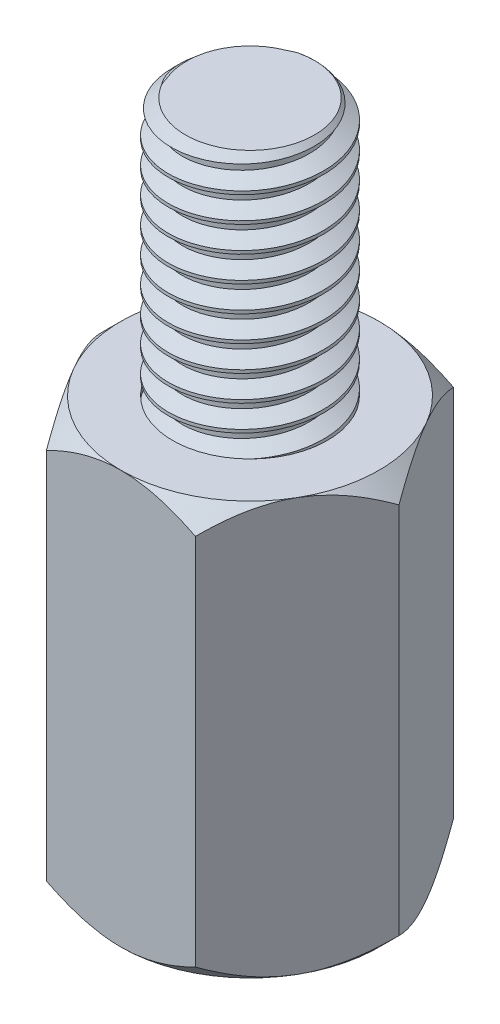
SolidWorks part; units mm, degrees
material "201 Acier inoxydable recuit (SS)"
ref_plane "Plan de face" through (0, 0, 0) normal (0, 0, 1) x (1, 0, 0)
ref_plane "Plan de dessus" through (0, 0, 0) normal (0, 1, 0) x (1, 0, 0)
ref_plane "Plan de droite" through (0, 0, 0) normal (1, 0, 0) x (0, 0, -1)
sketch "Esquisse1" plane through (0, 0, 0) normal (0, 1, 0) x (1, 0, 0)
  line L0 (-4.8113, 0) -> (4.4676, 0) construction
  line L1 (-2.8868, 0) -> (-1.4434, -2.5)
  line L2 (-1.4434, -2.5) -> (1.4434, -2.5)
  line L3 (1.4434, -2.5) -> (2.8868, 0)
  line L4 (2.8868, 0) -> (1.4434, 2.5)
  line L5 (1.4434, 2.5) -> (-1.4434, 2.5)
  line L6 (-1.4434, 2.5) -> (-2.8868, 0)
  line L7 (0, 4.1067) -> (0, -3.6256) construction
  circle A0 centre (0, 0) radius 2.5 construction
  dimension "D1" = 5
extrude "Adjustable height" add sketch "Esquisse1" along normal blind 4 and the other way blind 4
hole_wizard "Trou taraudé M31" positions "Esquisse2" profile "Esquisse3" tap size "M3" standard "ISO"
sketch "Esquisse2" plane through (0, -4, 0) normal (0, -1, 0) x (-1, 0, 0)
  point P0 (0, 0)
cosmetic thread "Filetage de perçage1" parameters "D1"=19.5, "D2"=3
sketch "Esquisse3" plane through (0, -4, 0) normal (1, 0, 0) x (0, 0, -1)
  line L0 (0, 0) -> (0, 20.7511)
  line L1 (0, 20.7511) -> (1.25, 20)
  line L2 (1.25, 20) -> (1.25, 0.5)
  line L3 (1.25, 0.5) -> (1.75, 0)
  line L5 (1.75, 0) -> (0, 0)
  line L6 (-1.25, 0.5) -> (-1.75, 0) construction
  line L10 (0, 20.7511) -> (-1.25, 20) construction
  line L11 (0, -6.35) -> (0, 107.95) construction
  dimension "Diamètre du trou pour taraudage" = 2.5
  dimension "Profondeur du trou pour taraudage" = 20
  dimension "Diamètre du fraisage entrant" = 3.5
  dimension "Angle du fraisage entrant" = 90
  dimension "Angle de pointe" = 118
sketch "Esquisse5" plane through (0, 0, 0) normal (1, 0, 0) x (0, 0, -1)
  line L0 (-2.5, 4) -> (-3.5, 3)
  line L1 (0, 4) -> (0, -4) construction
  line L2 (-3.5, 3) -> (-3.5, 4)
  line L3 (-3.5, 4) -> (-2.5, 4)
  line L4 (0, 23.8266) -> (0, -25.6452) construction
  line L5 (-7.434, 0) -> (6.7788, 0) construction
  line L6 (-3.5, -3) -> (-3.5, -4)
  line L7 (-2.5, -4) -> (-3.5, -3)
  line L8 (-3.5, -4) -> (-2.5, -4)
  dimension "D1" = 45
  dimension "D2" = 1
revolve "Enlèvement de matière-Révolution1" cut sketch "Esquisse5" angle 360 about L4
sketch "Esquisse6" plane through (0, 4, 0) normal (0, 1, 0) x (1, 0, 0)
  circle A0 centre (0, 0) radius 1.5
  dimension "D1" = 3
extrude "Boss.-Extru.1" add sketch "Esquisse6" along normal blind 5
chamfer "Chanfrein1" distance 0.25 angle 45 1 edges at (0, 9, 1.5)
ref_plane "Fond de filetage" through (0, 4.25, 0) normal (0, 1, 0) x (1, 0, 0)
thread "Filetage3" pitch 0.5 method cut profile "Profil de filetage6" start angle 0, offset 1, length 0, pitch 0.5, diameter 3
ref_plane "Plan8" through (-1.5, 9.75, 0) normal (0, 0, 1) x (-1, 0, 0)
sketch "Profil de filetage6" plane through (-1.5, 9.75, 0) normal (0, 0, 1) x (-1, 0, 0)
  line L0 (0, 0) -> (0, 0.5) construction
  line L11 (0, 0) -> (0, 0.4375)
  line L12 (0, 0.4375) -> (-0.2706, 0.2812)
  line L13 (-0.2706, 0.2812) -> (-0.2706, 0.1562)
  line L15 (-0.2706, 0.1562) -> (0, 0)
  line L17 (-0.2706, 0.2187) -> (0, 0.2187) construction
  point P2 (0, 0)
  dimension "Pitch" = 0.5
  dimension "Profile_Angle" = 60
  dimension "Profile_Land" = 0.125
  dimension "Profile_Height" = 0.2706
